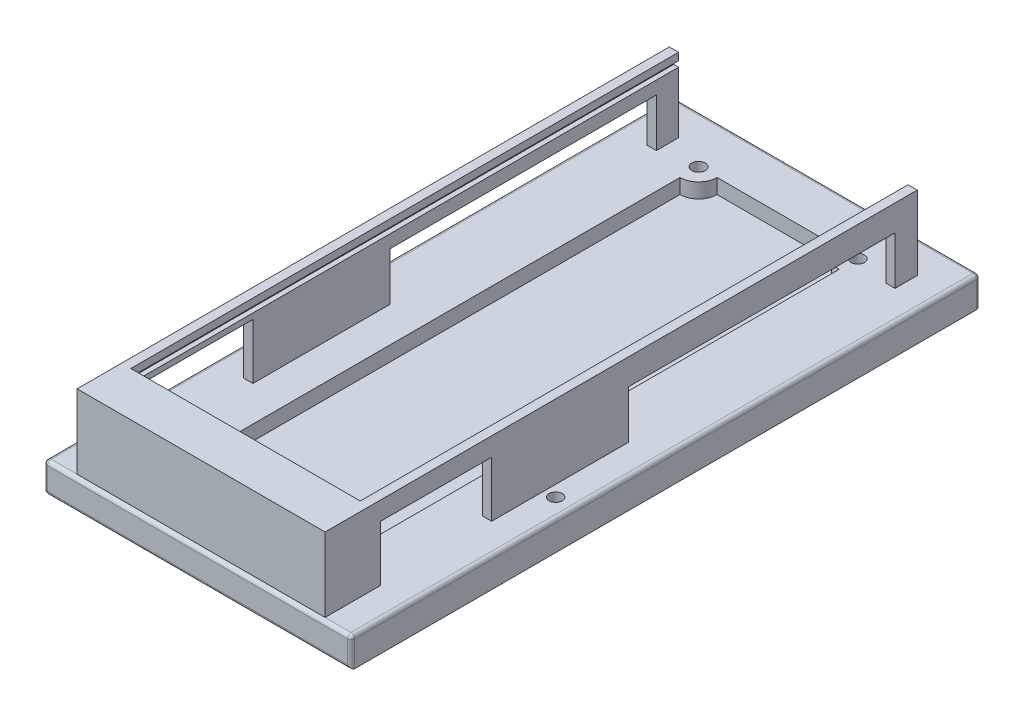
SolidWorks part; units mm, degrees
ref_plane "Front Plane" through (0, 0, 0) normal (0, 0, 1) x (1, 0, 0)
ref_plane "Top Plane" through (0, 0, 0) normal (0, 1, 0) x (1, 0, 0)
ref_plane "Right Plane" through (0, 0, 0) normal (1, 0, 0) x (0, 0, -1)
sketch "Sketch1" plane through (0, 0, 0) normal (0, 1, 0) x (1, 0, 0)
  line L0 (41.5, 95) -> (41.5, 0) construction
  line L1 (0, 0) -> (83, 0)
  line L2 (0, 0) -> (0, 170)
  line L3 (0, 170) -> (83, 170)
  line L4 (83, 0) -> (83, 170)
  line L5 (20, 156.9) -> (20, 13.1) construction
  circle A0 centre (5, 60.3) radius 1.75
  circle A1 centre (20, 13.1) radius 1.65 construction
  circle A2 centre (20, 156.9) radius 1.65 construction
  circle A3 centre (78, 60.3) radius 1.75
  circle A4 centre (63, 13.1) radius 1.65 construction
  circle A5 centre (63, 156.9) radius 1.65 construction
  point P19 (20, 85)
  point P20 (41.5, 0)
  point P21 (0, 85)
  dimension "D2" = 36.5
  dimension "D3" = 3.5
  dimension "D5" = 47.2
  dimension "D6" = 21.5
  dimension "D7" = 3.3
  dimension "D9" = 143.8
  dimension "D10" = 3.3
  dimension "D1" = 83
  dimension "D4" = 170
extrude "Boss-Extrude1" add sketch "Sketch1" along normal blind 8
sketch "Sketch3" plane through (0, 0, 0) normal (0, -1, 0) x (1, 0, 0)
  point P0 (20, -13.1)
  point P1 (63, -13.1)
  point P3 (63, -156.9)
  point P5 (20, -156.9)
hole_wizard "CBORE for M3 SHCS1" positions "Sketch3" profile "Sketch4" counterbore size "M3" standard "ANSI Metric" end condition through all
sketch "Sketch4" plane through (20, 0, -13.1) normal (1, 0, 0) x (0, 0, -1)
  line L0 (0, 0) -> (0, 8)
  line L1 (0, 8) -> (1.8, 8)
  line L3 (1.8, 8) -> (1.8, 3)
  line L4 (1.8, 3) -> (3.25, 3)
  line L5 (3.25, 3) -> (3.25, 0)
  line L7 (3.25, 0) -> (0, 0)
  line L11 (0, -6.35) -> (0, 107.95) construction
  dimension "Thru Hole Dia." = 3.6
  dimension "Thru Hole Depth" = 8
  dimension "C'Bore Dia." = 6.5
  dimension "C'Bore Depth" = 3
sketch "Sketch5" plane through (0, 8, 0) normal (0, 1, 0) x (1, 0, 0)
  line L5 (25, 156.9) -> (58, 156.9)
  line L6 (20, 151.9) -> (20, 18.1)
  line L11 (25, 13.1) -> (58, 13.1)
  line L12 (63, 151.9) -> (63, 18.1)
  arc A0 (20, 151.9) -> (25, 156.9) centre (20, 156.9) ccw
  arc A1 (58, 156.9) -> (63, 151.9) centre (63, 156.9) ccw
  arc A2 (63, 18.1) -> (58, 13.1) centre (63, 13.1) ccw
  arc A7 (25, 13.1) -> (20, 18.1) centre (20, 13.1) ccw
  point P0 (20, 156.9)
  point P1 (63, 156.9)
  point P2 (63, 13.1)
  point P3 (20, 13.1)
extrude "Cut-Extrude1" cut sketch "Sketch5" against normal blind 4
sketch "Sketch6" plane through (0, 0, 0) normal (0, -1, 0) x (1, 0, 0)
  line L1 (12, -95) -> (17, -95)
  line L2 (12, -95) -> (12, -115)
  line L3 (12, -115) -> (17, -115)
  line L4 (17, -95) -> (17, -115)
  dimension "D1" = 5
  dimension "D2" = 20
  dimension "D3" = 8
  dimension "D4" = 34.7
extrude "Boss-Extrude2" add sketch "Sketch6" along normal blind 8.8
sketch "Sketch7" plane through (0, 0, -115) normal (0, 0, -1) x (-1, 0, 0)
  line L0 (-17, -8.8) -> (-17, 0) construction
  line L1 (-12, 0) -> (-15.2, 0)
  line L2 (-12, 0) -> (-12, -6.8)
  line L3 (-12, -6.8) -> (-15.2, -6.8)
  line L4 (-15.2, 0) -> (-15.2, -6.8)
  dimension "D1" = 6.8
  dimension "D2" = 1.8
extrude "Cut-Extrude2" cut sketch "Sketch7" against normal through all
fillet "Fillet1" radius 6 1 edges at (17, 0, -105) second distance 8 first distance on face at (41.5, 0, -85)
fillet "Fillet2" radius 1 10 edges at (0, 4, 0) (41.5, 8, 0) (83, 4, 0) (83, 4, -170) (83, 8, -85) (41.5, 8, -170) (0, 4, -170) (0, 8, -85) (0, 0, -85) (41.5, 0, 0)
sketch "Sketch8" plane through (0, 8, 0) normal (0, 1, 0) x (1, 0, 0)
  line L1 (8, 161) -> (75, 161)
  line L2 (8, 161) -> (8, 1)
  line L3 (8, 1) -> (75, 1)
  line L4 (75, 161) -> (75, 1)
  line L6 (1, 1) -> (82, 1) construction
  circle A4 centre (5, 60.3) radius 1.75 construction
  dimension "D1" = 3
  dimension "D3" = 160
  dimension "D2" = 3
  dimension "D4" = 0
extrude "Boss-Extrude4" add sketch "Sketch8" along normal blind 20
sketch "Sketch11" plane through (0, 0, -161) normal (0, 0, -1) x (-1, 0, 0)
  line L0 (-75, 8) -> (-8, 8) construction
  line L1 (-72.5, 8) -> (-10.5, 8)
  line L2 (-72.5, 8) -> (-72.5, 24.5)
  line L3 (-72.5, 28) -> (-10.5, 28)
  line L4 (-10.5, 8) -> (-10.5, 24.5)
  line L5 (-75, 28) -> (-75, 8) construction
  line L6 (-8, 28) -> (-8, 8) construction
  line L7 (-75, 28) -> (-8, 28) construction
  line L8 (-10.5, 24.5) -> (-9.2, 24.5)
  line L9 (-73.8, 26) -> (-72.5, 26)
  line L10 (-73.8, 26) -> (-73.8, 24.5)
  line L11 (-73.8, 24.5) -> (-72.5, 24.5)
  line L12 (-9.2, 26) -> (-9.2, 24.5)
  line L13 (-10.5, 26) -> (-9.2, 26)
  line L14 (-72.5, 26) -> (-72.5, 28)
  line L15 (-10.5, 26) -> (-10.5, 28)
  dimension "D1" = 2.5
  dimension "D2" = 2.5
  dimension "D3" = 0
  dimension "D4" = 1.2
  dimension "D5" = 1.5
  dimension "D6" = 1.2
  dimension "D7" = 2
extrude "Cut-Extrude3" cut sketch "Sketch11" against normal blind 148
sketch "Sketch12" plane through (0, 0, -13) normal (0, 0, -1) x (-1, 0, 0)
  line L1 (-73.8, 26) -> (-9.2, 26)
  line L2 (-73.8, 26) -> (-73.8, 24.5)
  line L3 (-73.8, 24.5) -> (-9.2, 24.5)
  line L4 (-9.2, 26) -> (-9.2, 24.5)
extrude "Cut-Extrude4" cut sketch "Sketch12" against normal blind 1
sketch "Sketch15" plane through (75, 0, 0) normal (1, 0, 0) x (0, 0, -1)
  line L0 (1, 8) -> (169, 8) construction
  line L1 (128, 8) -> (110, 8)
  line L2 (128, 8) -> (128, 21) construction
  line L3 (128, 21) -> (110, 21)
  line L4 (110, 8) -> (110, 21) construction
  line L5 (101, 21) -> (110, 21)
  line L6 (1, 8) -> (161, 8) construction
  line L7 (101, 8) -> (83, 8)
  line L8 (101, 8) -> (101, 21) construction
  line L9 (101, 21) -> (83, 21)
  line L10 (83, 8) -> (83, 21)
  line L12 (101, 8) -> (110, 8)
  line L13 (128, 21) -> (137, 21)
  line L14 (137, 21) -> (155, 21)
  line L15 (137, 21) -> (137, 8) construction
  line L16 (137, 8) -> (155, 8)
  line L17 (155, 21) -> (155, 8)
  line L18 (128, 8) -> (137, 8)
  line L20 (161, 28) -> (161, 8) construction
  dimension "D1" = 18
  dimension "D2" = 13
  dimension "D3" = 6
  dimension "D4" = 18
  dimension "D5" = 13
  dimension "D6" = 9
  dimension "D7" = 18
  dimension "D8" = 13
  dimension "D9" = 9
extrude "Cut-Extrude5" cut sketch "Sketch15" against normal through all and the other way through all
sketch "Sketch16" plane through (75, 0, 0) normal (1, 0, 0) x (0, 0, -1)
  line L0 (1, 8) -> (169, 8) construction
  line L1 (16, 8) -> (46, 8)
  line L2 (16, 8) -> (16, 23)
  line L3 (16, 23) -> (46, 23)
  line L4 (46, 8) -> (46, 23)
  line L5 (1, 28) -> (1, 8) construction
  point P8 (16, 15.5)
  dimension "D1" = 15
  dimension "D2" = 30
  dimension "D3" = 15
extrude "Cut-Extrude6" cut sketch "Sketch16" against normal through all
